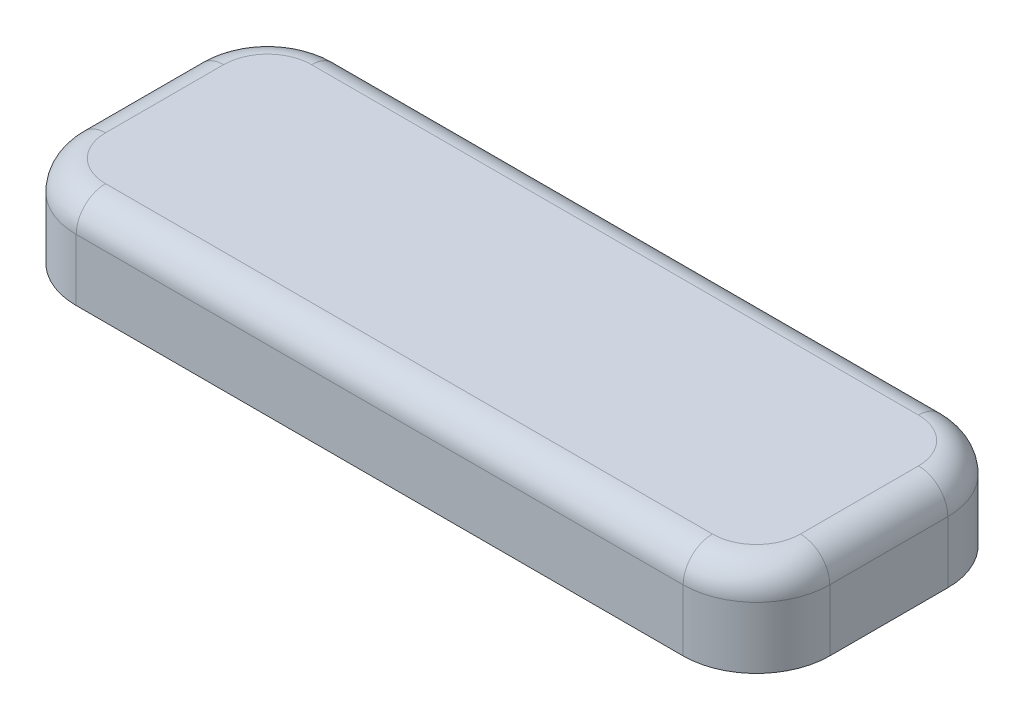
SolidWorks part; units mm, degrees
ref_plane "前视基准面" through (0, 0, 0) normal (0, 0, 1) x (1, 0, 0)
ref_plane "上视基准面" through (0, 0, 0) normal (0, 1, 0) x (1, 0, 0)
ref_plane "右视基准面" through (0, 0, 0) normal (1, 0, 0) x (0, 0, -1)
other "Configuration Table"
sketch "草图1" plane through (0, 0, 0) normal (0, 1, 0) x (1, 0, 0)
  line L0 (-2.2, 0) -> (2.2, 0) construction
  line L1 (0, 2.2) -> (0, -2.2) construction
  line L2 (2.2, 0.6) -> (2.2, -0.6)
  line L3 (-0.6, 2.2) -> (0.6, 2.2)
  line L4 (-2.2, -0.6) -> (-2.2, 0.6)
  line L5 (-0.6, -2.2) -> (0.6, -2.2)
  line L6 (-0.6, 2.2) -> (-0.6, 0.6)
  line L7 (-0.6, 0.6) -> (-2.2, 0.6)
  line L8 (-2.2, -0.6) -> (-0.6, -0.6)
  line L9 (-0.6, -0.6) -> (-0.6, -2.2)
  line L10 (0.6, -2.2) -> (0.6, -0.6)
  line L11 (0.6, -0.6) -> (2.2, -0.6)
  line L12 (2.2, 0.6) -> (0.6, 0.6)
  line L13 (0.6, 0.6) -> (0.6, 2.2)
  line L14 (-11.9062, 0) -> (11.9062, 0) construction
  line L15 (-14.1063, 0) -> (-9.7062, 0) construction
  line L16 (-11.9062, 2.2) -> (-11.9062, -2.2) construction
  line L17 (-14.1063, -0.6) -> (-14.1063, 0.6)
  line L18 (-12.5062, -2.2) -> (-11.3063, -2.2)
  line L19 (-11.3063, 2.2) -> (-12.5062, 2.2)
  line L20 (-9.7062, -0.6) -> (-9.7062, 0.6)
  line L21 (-14.1063, -0.6) -> (-12.5062, -0.6)
  line L22 (-12.5062, -0.6) -> (-12.5062, -2.2)
  line L23 (-11.3063, -2.2) -> (-11.3063, -0.6)
  line L24 (-11.3063, -0.6) -> (-9.7062, -0.6)
  line L25 (-9.7062, 0.6) -> (-11.3063, 0.6)
  line L26 (-11.3063, 0.6) -> (-11.3063, 2.2)
  line L27 (-12.5062, 2.2) -> (-12.5062, 0.6)
  line L28 (-12.5062, 0.6) -> (-14.1063, 0.6)
  line L29 (9.7062, 0) -> (14.1063, 0) construction
  line L30 (11.9062, -2.2) -> (11.9062, 2.2) construction
  line L31 (9.7062, 0.6) -> (9.7062, -0.6)
  line L32 (11.3063, 2.2) -> (12.5062, 2.2)
  line L33 (14.1063, -0.6) -> (14.1063, 0.6)
  line L34 (11.3063, -2.2) -> (12.5062, -2.2)
  line L35 (9.7062, 0.6) -> (11.3063, 0.6)
  line L36 (11.3063, 0.6) -> (11.3063, 2.2)
  line L37 (12.5062, 2.2) -> (12.5062, 0.6)
  line L38 (12.5062, 0.6) -> (14.1063, 0.6)
  line L39 (14.1063, -0.6) -> (12.5062, -0.6)
  line L40 (12.5062, -0.6) -> (12.5062, -2.2)
  line L41 (11.3063, -2.2) -> (11.3063, -0.6)
  line L42 (11.3063, -0.6) -> (9.7062, -0.6)
  circle A0 centre (0, 0) radius 2.8
  circle A1 centre (-11.9062, 0) radius 2.8
  circle A2 centre (11.9062, 0) radius 2.8
  point P4 (0, 0)
  point P7 (0, 0)
  point P10 (2.2, 0)
  point P13 (0, 2.2)
  point P16 (-2.2, 0)
  point P19 (0, -2.2)
  point P28 (0, 0)
  point P31 (-11.9062, 0)
  point P34 (-11.9062, 0)
  point P37 (-14.1063, 0)
  point P40 (-11.9062, -2.2)
  point P43 (-11.9062, 2.2)
  point P46 (-9.7062, 0)
  point P54 (11.9062, 0)
  point P57 (11.9062, 0)
  point P60 (9.7062, 0)
  point P63 (11.9062, 2.2)
  point P66 (14.1063, 0)
  point P69 (11.9062, -2.2)
  dimension "D7" = 5.6
  dimension "D15" = 5.6
  dimension "D22" = 5.6
  dimension "D1" = 4.4
  dimension "D2" = 4.4
  dimension "D3" = 1.2
  dimension "D4" = 1.2
  dimension "D5" = 1.2
  dimension "D6" = 1.2
  dimension "D8" = 23.8125
  dimension "D9" = 4.4
  dimension "D10" = 4.4
  dimension "D11" = 1.2
  dimension "D12" = 1.2
  dimension "D13" = 1.2
  dimension "D14" = 1.2
  dimension "D16" = 4.4
  dimension "D17" = 4.4
  dimension "D18" = 1.2
  dimension "D19" = 1.2
  dimension "D20" = 1.2
  dimension "D21" = 1.2
extrude "凸台-拉伸1" add sketch "草图1" against normal blind 5 contours A0 | L8 L9 L5 L10 L11 L2 L12 L13 L3 L6 L7 L4
sketch "草图2" plane through (0, 0, 0) normal (0, 1, 0) x (1, 0, 0)
  line L0 (0, -9.025) -> (0, 9.025) construction
  line L1 (-25.6938, 9.025) -> (25.6938, 9.025)
  line L2 (-25.6938, -9.025) -> (25.6938, -9.025)
  line L3 (-25.6938, 9.025) -> (-25.6938, -9.025)
  line L4 (25.6938, 9.025) -> (25.6938, -9.025)
  point P4 (0, 0)
  point P8 (0, 9.025)
  point P11 (0, -9.025)
  dimension "D1" = 18.05
  dimension "D2" = 51.3875
extrude "凸台-拉伸2" add sketch "草图2" along normal blind 1.2
sketch "草图3" plane through (0, 0, 0) normal (0, 1, 0) x (1, 0, 0)
  line L4 (25.6938, -9.025) -> (25.6938, 9.025)
  line L5 (-25.6938, -9.025) -> (25.6938, -9.025)
  line L6 (-25.6938, 9.025) -> (-25.6938, -9.025)
  line L7 (25.6938, 9.025) -> (-25.6938, 9.025)
  line L8 (25.6938, -9.025) -> (25.6938, 9.025)
  line L9 (-25.6938, -9.025) -> (25.6938, -9.025)
  line L10 (-25.6938, 9.025) -> (-25.6938, -9.025)
  line L11 (25.6938, 9.025) -> (-25.6938, 9.025)
  line L20 (24.4938, -7.825) -> (24.4938, 7.825)
  line L21 (24.4938, 7.825) -> (-24.4938, 7.825)
  line L22 (-24.4938, 7.825) -> (-24.4938, -7.825)
  line L23 (-24.4938, -7.825) -> (24.4938, -7.825)
  line L24 (24.4938, -7.825) -> (24.4938, 7.825)
  line L25 (24.4938, 7.825) -> (-24.4938, 7.825)
  line L26 (-24.4938, 7.825) -> (-24.4938, -7.825)
  line L27 (-24.4938, -7.825) -> (24.4938, -7.825)
  dimension "D1" = 0
  dimension "D2" = 1.2
extrude "凸台-拉伸3" add sketch "草图3" against normal blind 5
fillet "圆角1" radius 5 8 edges at (-25.6938, -1.9, -9.025) (25.6938, -1.9, -9.025) (25.6938, -1.9, 9.025) (-25.6938, -1.9, 9.025) (-24.4938, -2.5, -7.825) (24.4938, -2.5, -7.825) (24.4938, -2.5, 7.825) (-24.4938, -2.5, 7.825)
fillet "圆角2" radius 2 16 edges at (24.4938, 0, 0) (0, 0, 7.825) (0, 0, -7.825) (-24.4938, 0, 0) (24.2293, 1.2, -7.5605) (25.6938, 1.2, 0) (24.2293, 1.2, 7.5605) (0, 1.2, 9.025) (-24.2293, 1.2, 7.5605) (-25.6938, 1.2, 0) (-24.2293, 1.2, -7.5605) (0, 1.2, -9.025) (23.0293, 0, 6.3605) (23.0293, 0, -6.3605) (-23.0293, 0, -6.3605) (-23.0293, 0, 6.3605)
extrude "凸台-拉伸4" add sketch "草图1<3>" against normal blind 5 contours A2 | L42 L31 L35 L36 L32 L37 L38 L33 L39 L40 L34 L41
sketch "草图1<3>" plane through (0, 0, 0) normal (0, 1, 0) x (1, 0, 0) same geometry as "草图1"
extrude "凸台-拉伸5" add sketch "草图1<4>" against normal blind 5 contours A1 | L18 L23 L24 L20 L25 L26 L19 L27 L28 L17 L21 L22
sketch "草图1<4>" plane through (0, 0, 0) normal (0, 1, 0) x (1, 0, 0) same geometry as "草图1"
chamfer "倒角3" distance 0.5 angle 45 3 edges at (-11.9062, 0, 2.8) (0, 0, 2.8) (11.9062, 0, 2.8)
